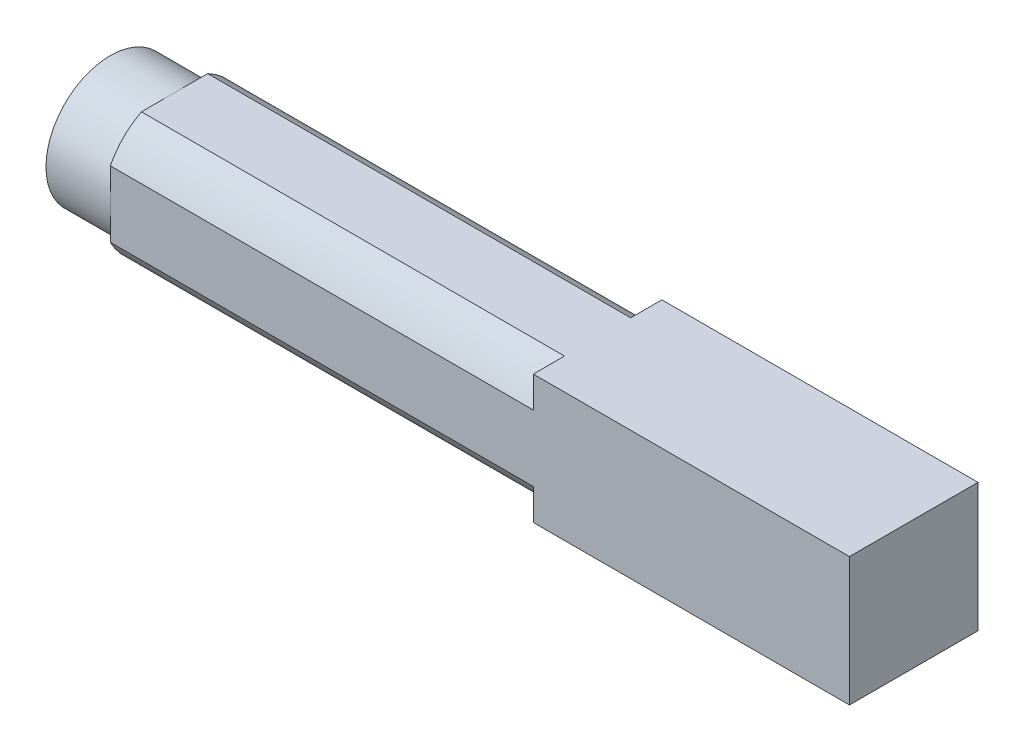
SolidWorks part; units mm, degrees
ref_plane "Front Plane" through (0, 0, 0) normal (0, 0, 1) x (1, 0, 0)
ref_plane "Top Plane" through (0, 0, 0) normal (0, 1, 0) x (1, 0, 0)
ref_plane "Right Plane" through (0, 0, 0) normal (1, 0, 0) x (0, 0, -1)
sketch "Sketch1" plane through (0, 0, 0) normal (1, 0, 0) x (0, 0, -1)
  line L1 (-3.175, -3.175) -> (3.175, -3.175)
  line L2 (-3.175, -3.175) -> (-3.175, 3.175)
  line L3 (-3.175, 3.175) -> (3.175, 3.175)
  line L4 (3.175, -3.175) -> (3.175, 3.175)
  line L5 (-3.175, -3.175) -> (3.175, 3.175) construction
  line L6 (-3.175, 3.175) -> (3.175, -3.175) construction
  point P0 (0, 0)
  dimension "D1" = 6.35
extrude "Boss-Extrude1" add sketch "Sketch1" along normal blind 39.6875
ref_axis "Axis1" through (0, 0, 0) along (1, 0, 0)
ref_plane "Plane1" through (24.0716, 0, 0) normal (-1, 0, 0) x (0, 0, 1)
sketch "Sketch4" plane through (0, 0, 0) normal (-1, 0, 0) x (0, 0, 1)
  line L1 (-5.5323, -4.0531) -> (5.5323, -4.0531)
  line L2 (-5.5323, -4.0531) -> (-5.5323, 4.0531)
  line L3 (-5.5323, 4.0531) -> (5.5323, 4.0531)
  line L4 (5.5323, -4.0531) -> (5.5323, 4.0531)
  line L5 (-5.5323, -4.0531) -> (5.5323, 4.0531) construction
  line L6 (-5.5323, 4.0531) -> (5.5323, -4.0531) construction
  circle A0 centre (0, 0) radius 3.175
  dimension "D1" = 6.35
extrude "Cut-Extrude3" cut sketch "Sketch4" against normal blind 3.175
sketch "Sketch5" plane through (3.175, 0, 0) normal (-1, 0, 0) x (0, 0, 1)
  line L1 (-4.6082, -4.6911) -> (4.6082, -4.6911)
  line L2 (-4.6082, -4.6911) -> (-4.6082, 4.6911)
  line L3 (-4.6082, 4.6911) -> (4.6082, 4.6911)
  line L4 (4.6082, -4.6911) -> (4.6082, 4.6911)
  line L5 (-4.6082, -4.6911) -> (4.6082, 4.6911) construction
  line L6 (-4.6082, 4.6911) -> (4.6082, -4.6911) construction
  circle A0 centre (0, 0) radius 3.5719
  dimension "D1" = 7.1437
extrude "Cut-Extrude4" cut sketch "Sketch5" against normal up to surface (20.8966 mm away)
